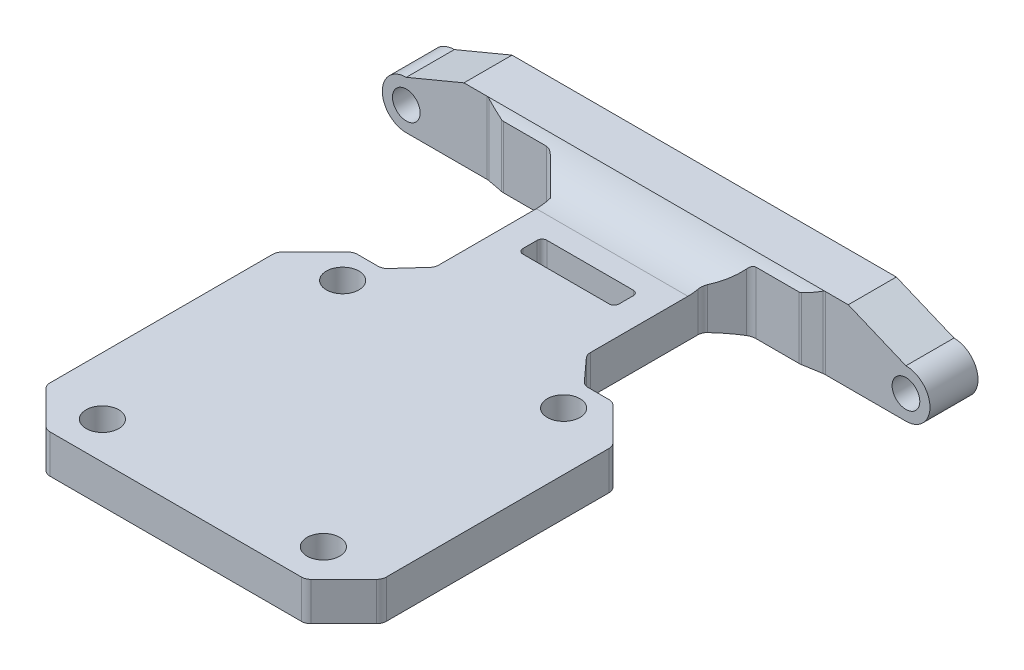
SolidWorks part; units mm, degrees
ref_plane "前视基准面" through (0, 0, 0) normal (0, 0, 1) x (1, 0, 0)
ref_plane "上视基准面" through (0, 0, 0) normal (0, 1, 0) x (1, 0, 0)
ref_plane "右视基准面" through (0, 0, 0) normal (1, 0, 0) x (0, 0, -1)
other "Configuration Table"
sketch "草图1" plane through (0, 0, 0) normal (0, 0, 1) x (1, 0, 0)
  line L0 (-26, 0) -> (26, 0) construction
  line L2 (-26, -2.5) -> (26, -2.5)
  line L3 (0, 0) -> (0, 20.5752) construction
  line L4 (-26, 2.5) -> (-20, 5)
  line L5 (-20, 5) -> (20, 5)
  line L6 (26, 2.5) -> (20, 5)
  arc A0 (-26, 2.5) -> (-26, -2.5) centre (-26, 0) ccw
  arc A1 (26, -2.5) -> (26, 2.5) centre (26, 0) ccw
  circle A2 centre (-26, 0) radius 1.4408
  circle A3 centre (26, 0) radius 1.4408
  point P2 (0, 0)
  point P20 (0, 5)
  dimension "D1" = 2.5
  dimension "D3" = 20
  dimension "D2" = 52
  dimension "D4" = 5
extrude "凸台-拉伸1" add sketch "草图1" along normal blind 5
sketch "草图3" plane through (0, 0, 5) normal (0, 0, 1) x (1, 0, 0)
  line L1 (17.5, -2) -> (-17.5, -2)
  line L2 (17.5, -2) -> (17.5, 2)
  line L3 (17.5, 2) -> (-17.5, 2)
  line L4 (-17.5, -2) -> (-17.5, 2)
  line L5 (17.5, -2) -> (-17.5, 2) construction
  line L6 (17.5, 2) -> (-17.5, -2) construction
  point P0 (0, 0)
  dimension "D1" = 4
  dimension "D2" = 35
extrude "凸台-拉伸2" add sketch "草图3" along normal blind 50
fillet "圆角1" radius 10 1 edges at (0, -2, 5)
fillet "圆角2" radius 5 1 edges at (0, 2, 5)
sketch "草图4" plane through (0, -2, 0) normal (0, -1, 0) x (1, 0, 0)
  line L1 (-13.5, 55) -> (-17.5, 55)
  line L4 (-17.5, 55) -> (-17.5, 51)
  line L5 (0, 0) -> (0, 19.1677) construction
  line L15 (-13.5, 55) -> (-17.5, 51)
  line L16 (-17.5, 55) -> (17.5, 55) construction
  line L17 (-17.5, 55) -> (-17.5, 8.1225) construction
  line L18 (-17.5, 51) -> (-17.5, 27)
  line L19 (-17.5, 27) -> (-13.5, 23)
  line L20 (-13.5, 23) -> (-10.5, 23)
  line L21 (-7.8888, 20.1225) -> (-7.8888, 8.1225)
  line L22 (-17.5, 8.1225) -> (17.5, 8.1225) construction
  line L23 (-7.8888, 8.1225) -> (-10.5, 5.5113)
  line L24 (-10.5, 5.5113) -> (-15.5, 5.5113)
  line L25 (-15.5, 5.5113) -> (-17.5, 5)
  line L26 (-10.5, 23) -> (-7.8888, 20.1225)
  line L27 (-17.5, 27) -> (-17.5, 5)
  line L28 (17.5, 27) -> (17.5, 5)
  line L29 (15.5, 5.5113) -> (17.5, 5)
  line L30 (10.5, 5.5113) -> (15.5, 5.5113)
  line L31 (7.8888, 8.1225) -> (10.5, 5.5113)
  line L32 (7.8888, 20.1225) -> (7.8888, 8.1225)
  line L33 (10.5, 23) -> (7.8888, 20.1225)
  line L34 (13.5, 23) -> (10.5, 23)
  line L35 (17.5, 27) -> (13.5, 23)
  line L36 (17.5, 55) -> (17.5, 51)
  line L37 (13.5, 55) -> (17.5, 55)
  line L38 (13.5, 55) -> (17.5, 51)
  dimension "D1" = 4
  dimension "D2" = 4
  dimension "D3" = 4
  dimension "D4" = 4
  dimension "D5" = 12
  dimension "D6" = 22
  dimension "D7" = 7
  dimension "D8" = 2
  dimension "D9" = 7
extrude "切除-拉伸2" cut sketch "草图4" against normal through all both and the other way through all
sketch "草图5" plane through (0, -2, 0) normal (0, -1, 0) x (1, 0, 0)
  line L0 (0, 16.7393) -> (0, 7.7169) construction
  line L1 (-20.4211, 38.6281) -> (24.0057, 38.6281) construction
  line L2 (-7.8888, 8.1225) -> (7.8888, 8.1225) construction
  line L9 (-5, 11.8725) -> (5, 11.8725)
  line L10 (-5, 11.8725) -> (-5, 14.3725)
  line L11 (-5, 14.3725) -> (5, 14.3725)
  line L12 (5, 11.8725) -> (5, 14.3725)
  line L13 (-5, 11.8725) -> (5, 14.3725) construction
  line L14 (-5, 14.3725) -> (5, 11.8725) construction
  circle A0 centre (-11.5, 26.1281) radius 1.7
  circle A1 centre (11.5, 26.1281) radius 1.7
  circle A2 centre (11.5, 51.1281) radius 1.7
  circle A3 centre (-11.5, 51.1281) radius 1.7
  point P1 (0, 22.5936)
  point P18 (0, 13.1225)
  dimension "D1" = 23
  dimension "D2" = 25
  dimension "D3" = 3.4
  dimension "D4" = 5
  dimension "D6" = 10
  dimension "D7" = 2.5
extrude "切除-拉伸3" cut sketch "草图5" against normal up to next and the other way through all
fillet "圆角3" radius 0.5 4 edges at (5, 0, 11.8725) (-5, 0, 11.8725) (5, 0, 14.3725) (-5, 0, 14.3725)
fillet "圆角4" radius 1 19 edges at (17.5, 0, 51) (13.5, 0, 55) (17.5, 0, 27) (13.5, 0, 23) (10.5, 0, 23) (7.8888, 0, 20.1225) (7.8888, 0.109, 8.1225) (10.5, 0.8753, 5.5113) (15.5, 0.8753, 5.5113) (17.5, 1.25, 5) (-17.5, 1.25, 5) (-15.5, 0.8753, 5.5113) (-10.5, 0.8753, 5.5113) (-7.8888, 0, 20.1225) (-10.5, 0, 23) (-13.5, 0, 23) (-17.5, 0, 27) (-17.5, 0, 51) (-13.5, 0, 55)
